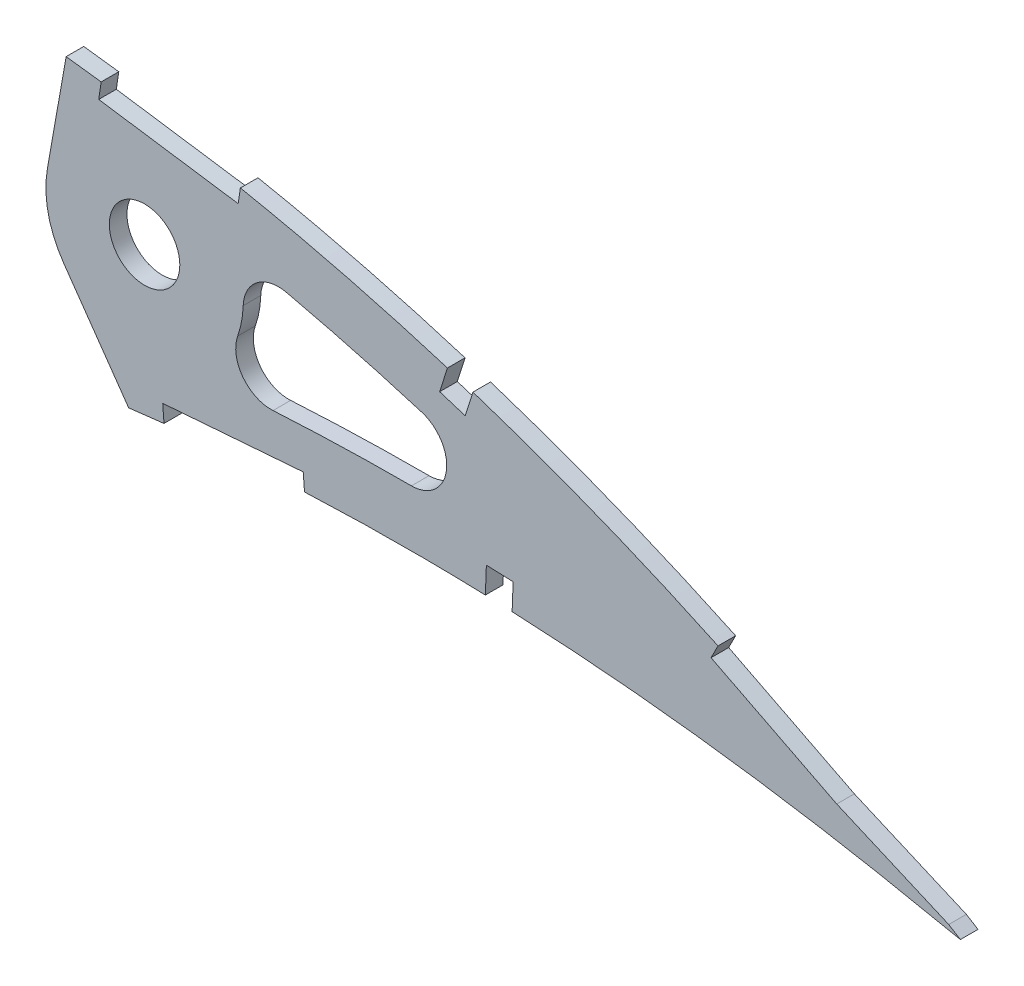
SolidWorks part; units mm, degrees
material "Pine"
ref_plane "Front Plane" through (0, 0, 0) normal (0, 0, 1) x (1, 0, 0)
ref_plane "Top Plane" through (0, 0, 0) normal (0, 1, 0) x (1, 0, 0)
ref_plane "Right Plane" through (0, 0, 0) normal (1, 0, 0) x (0, 0, -1)
curve "Curve2"
  spline degree 3 poles (520.229, 0.8111, 0) (520.1892, 0.8357, 0) (520.0299, 0.9341, 0) (519.6711, 1.1542, 0) (519.0735, 1.5208, 0) (518.237, 2.0313, 0) (517.1622, 2.6844, 0) (515.8486, 3.4756, 0) (514.2969, 4.4021, 0) (512.5075, 5.4598, 0) (510.4807, 6.6436, 0) (508.2172, 7.9486, 0) (505.7172, 9.3676, 0) (502.9816, 10.8948, 0) (500.0114, 12.5227, 0) (496.8072, 14.2443, 0) (493.3701, 16.0505, 0) (489.7015, 17.9338, 0) (485.8019, 19.8836, 0) (481.6733, 21.8919, 0) (477.317, 23.9487, 0) (472.7345, 26.0429, 0) (467.9284, 28.1661, 0) (462.9001, 30.305, 0) (457.6524, 32.4505, 0) (452.1876, 34.5902, 0) (446.5089, 36.7144, 0) (440.6184, 38.8094, 0) (434.5207, 40.866, 0) (428.2186, 42.8708, 0) (421.7166, 44.813, 0) (415.0186, 46.68, 0) (408.1302, 48.4622, 0) (401.0555, 50.1466, 0) (393.8008, 51.7219, 0) (386.3718, 53.1787, 0) (378.7746, 54.5024, 0) (371.0303, 55.692, 0) (363.2636, 56.6815, 0) (355.5128, 57.652, 0) (347.7736, 58.5637, 0) (339.9398, 59.4368, 0) (332.019, 60.2663, 0) (324.019, 61.0497, 0) (315.9478, 61.7836, 0) (307.814, 62.4658, 0) (299.6253, 63.0925, 0) (291.3904, 63.6628, 0) (283.1174, 64.1714, 0) (274.8152, 64.6183, 0) (266.4922, 65.0001, 0) (258.157, 65.3142, 0) (249.8185, 65.5589, 0) (241.4854, 65.7316, 0) (233.1666, 65.8314, 0) (224.8708, 65.8555, 0) (216.6071, 65.8035, 0) (208.384, 65.6736, 0) (200.2107, 65.464, 0) (192.0958, 65.1743, 0) (184.048, 64.8046, 0) (176.0762, 64.3519, 0) (168.189, 63.8191, 0) (160.3952, 63.2038, 0) (152.7034, 62.506, 0) (145.1216, 61.7286, 0) (137.6583, 60.8693, 0) (130.3214, 59.9308, 0) (123.1191, 58.9147, 0) (116.0593, 57.8206, 0) (109.1496, 56.6517, 0) (102.3976, 55.409, 0) (95.8102, 54.0963, 0) (89.3948, 52.714, 0) (83.1581, 51.266, 0) (77.1065, 49.7551, 0) (71.2467, 48.1838, 0) (65.5845, 46.5561, 0) (60.1256, 44.8756, 0) (54.8764, 43.1442, 0) (49.8409, 41.3683, 0) (45.0253, 39.5493, 0) (40.4333, 37.6928, 0) (36.0702, 35.8014, 0) (31.9393, 33.8806, 0) (28.0452, 31.9329, 0) (24.3908, 29.9636, 0) (20.9797, 27.9757, 0) (17.8153, 25.973, 0) (14.8987, 23.9604, 0) (12.2341, 21.9394, 0) (9.8224, 19.9149, 0) (7.6651, 17.8901, 0) (5.7652, 15.8664, 0) (4.1228, 13.8473, 0) (2.7399, 11.8344, 0) (1.6168, 9.8297, 0) (0.7561, 7.8345, 0) (0.1568, 5.85, 0) (-0.1712, 3.8792, 0) (-0.2528, 1.9205, 0) (-0.0842, 0.6392, 0) (0, 0, 0) knots 0 0 0 0 0.000254 0.001015 0.002283 0.004057 0.006331 0.009105 0.012374 0.016134 0.02038 0.025106 0.030306 0.035972 0.0421 0.048678 0.055702 0.06316 0.071046 0.07935 0.088063 0.097176 0.106678 0.116562 0.126814 0.137428 0.148394 0.1597 0.171338 0.183298 0.19557 0.208144 0.221012 0.234162 0.247587 0.261277 0.275223 0.289414 0.303771 0.317689 0.331784 0.34604 0.360444 0.374983 0.38964 0.404403 0.419257 0.434187 0.449177 0.464215 0.479284 0.49437 0.509458 0.524532 0.539579 0.554583 0.56953 0.584403 0.599191 0.613877 0.628447 0.642889 0.657186 0.671326 0.685294 0.699078 0.712665 0.726043 0.739198 0.752118 0.764792 0.777208 0.789356 0.801224 0.812804 0.824083 0.835055 0.84571 0.856038 0.866034 0.875689 0.884998 0.893953 0.902553 0.910789 0.918661 0.926166 0.933303 0.940071 0.946475 0.952518 0.958205 0.963547 0.968557 0.97325 0.977651 0.981787 0.985694 0.989415 0.993001 0.996508 1 1 1 1
curve "Curve3"
  spline degree 3 poles (0, 0, 0) (0.1336, -0.6306, 0) (0.4014, -1.8948, 0) (1.129, -3.7148, 0) (2.0912, -5.4642, 0) (3.3081, -7.1386, 0) (4.7718, -8.7374, 0) (6.479, -10.2623, 0) (8.428, -11.7125, 0) (10.6162, -13.0874, 0) (13.0406, -14.3883, 0) (15.6982, -15.6145, 0) (18.5868, -16.7656, 0) (21.7032, -17.8401, 0) (25.0435, -18.8396, 0) (28.6046, -19.7616, 0) (32.3825, -20.6074, 0) (36.3735, -21.375, 0) (40.5732, -22.065, 0) (44.9774, -22.6771, 0) (49.5814, -23.2117, 0) (54.3808, -23.6676, 0) (59.3708, -24.0458, 0) (64.5464, -24.3466, 0) (69.9027, -24.5709, 0) (75.4344, -24.718, 0) (81.1363, -24.7899, 0) (87.003, -24.788, 0) (93.0289, -24.7115, 0) (99.2088, -24.5648, 0) (105.5368, -24.3469, 0) (112.0073, -24.0604, 0) (118.6142, -23.7083, 0) (125.3518, -23.2917, 0) (132.2141, -22.8125, 0) (139.1951, -22.2745, 0) (146.2885, -21.679, 0) (153.4882, -21.0296, 0) (160.7876, -20.3295, 0) (168.1806, -19.5808, 0) (175.6606, -18.7872, 0) (183.2209, -17.9512, 0) (190.8551, -17.0772, 0) (198.5563, -16.1668, 0) (206.3179, -15.2253, 0) (214.1326, -14.2544, 0) (221.9939, -13.2579, 0) (229.8947, -12.2404, 0) (237.8276, -11.2019, 0) (245.786, -10.1497, 0) (253.7621, -9.0829, 0) (261.7491, -8.0072, 0) (269.7395, -6.9257, 0) (277.7256, -5.8389, 0) (285.7003, -4.7513, 0) (293.6562, -3.6657, 0) (301.5856, -2.5824, 0) (309.4812, -1.5067, 0) (317.3352, -0.4385, 0) (325.1402, 0.6201, 0) (332.8888, 1.6659, 0) (340.5737, 2.6975, 0) (348.187, 3.7144, 0) (355.721, 4.7168, 0) (363.0553, 5.6745, 0) (370.1707, 6.6383, 0) (377.0913, 7.4284, 0) (383.9258, 8.1028, 0) (390.6811, 8.6557, 0) (397.3493, 9.0951, 0) (403.9227, 9.4241, 0) (410.3934, 9.6473, 0) (416.7532, 9.7713, 0) (422.9943, 9.7993, 0) (429.1081, 9.7402, 0) (435.0867, 9.5987, 0) (440.9216, 9.3813, 0) (446.6049, 9.0952, 0) (452.1283, 8.7483, 0) (457.4837, 8.3456, 0) (462.6634, 7.8966, 0) (467.6597, 7.4078, 0) (472.4647, 6.8849, 0) (477.0715, 6.3387, 0) (481.4727, 5.7729, 0) (485.6616, 5.1968, 0) (489.6316, 4.6162, 0) (493.3764, 4.0385, 0) (496.89, 3.4693, 0) (500.1667, 2.916, 0) (503.2016, 2.384, 0) (505.9892, 1.8782, 0) (508.5257, 1.4052, 0) (510.8062, 0.9673, 0) (512.8275, 0.5717, 0) (514.5859, 0.2202, 0) (516.0789, -0.0824, 0) (517.3037, -0.3347, 0) (518.2586, -0.5328, 0) (518.9417, -0.6767, 0) (519.3522, -0.7624, 0) (519.5346, -0.8013, 0) (519.5802, -0.8111, 0) knots 0 0 0 0 0.003638 0.007293 0.011028 0.014901 0.018963 0.023258 0.027821 0.032679 0.037853 0.043362 0.049215 0.055422 0.061989 0.068918 0.076211 0.083868 0.091887 0.100266 0.109 0.118085 0.127515 0.137285 0.147388 0.157816 0.168563 0.179619 0.190977 0.202627 0.21456 0.226767 0.239236 0.251959 0.264924 0.27812 0.291536 0.30516 0.318981 0.332985 0.347163 0.361499 0.375981 0.390597 0.405333 0.420175 0.43511 0.450124 0.465203 0.480333 0.495501 0.51069 0.525887 0.541078 0.556247 0.571382 0.586466 0.601485 0.616424 0.631269 0.646007 0.660621 0.675098 0.689423 0.703582 0.716908 0.730009 0.742952 0.755726 0.76832 0.780724 0.792927 0.804916 0.816679 0.828204 0.839475 0.850481 0.861208 0.871639 0.881763 0.891564 0.901027 0.910139 0.918884 0.927249 0.935221 0.942785 0.949928 0.956638 0.962904 0.968712 0.974054 0.978918 0.983297 0.98718 0.990561 0.993433 0.995791 0.99763 0.998946 0.999737 1 1 1 1
sketch "Sketch1" plane through (0, 0, 0) normal (0, 0, 1) x (1, 0, 0)
  line L1 (502.7977, -0.7849) -> (507.4667, -1.7115)
  line L2 (503.4256, 0.7849) -> (507.4667, -1.7115)
  spline S2 degree 3 poles (0, 0) (0.1293, -0.6103) (0.3884, -1.8336) (1.0925, -3.5948) (2.0236, -5.2877) (3.2013, -6.908) (4.6177, -8.4552) (6.2698, -9.9309) (8.1558, -11.3342) (10.2733, -12.6647) (12.6193, -13.9236) (15.1912, -15.1102) (17.9865, -16.2241) (21.0022, -17.2639) (24.2346, -18.231) (27.6807, -19.1233) (31.3366, -19.9418) (35.1986, -20.6846) (39.2627, -21.3523) (43.5246, -21.9446) (47.9799, -22.4619) (52.6243, -22.9031) (57.4531, -23.2691) (62.4616, -23.5602) (67.6448, -23.7773) (72.9979, -23.9196) (78.5156, -23.9892) (84.1928, -23.9873) (90.0241, -23.9133) (96.0044, -23.7713) (102.128, -23.5605) (108.3894, -23.2833) (114.783, -22.9425) (121.303, -22.5394) (127.9436, -22.0756) (134.6991, -21.555) (141.5634, -20.9788) (148.5305, -20.3504) (155.5942, -19.6728) (162.7484, -18.9484) (169.9867, -18.1804) (177.3029, -17.3713) (184.6905, -16.5256) (192.1429, -15.6446) (199.6538, -14.7335) (207.2161, -13.794) (214.8235, -12.8296) (222.4691, -11.845) (230.1458, -10.84) (237.8471, -9.8218) (245.5656, -8.7896) (253.2946, -7.7486) (261.0269, -6.702) (268.755, -5.6503) (276.4722, -4.5978) (284.1711, -3.5473) (291.8444, -2.499) (299.485, -1.458) (307.0852, -0.4243) (314.6382, 0.6001) (322.1365, 1.6121) (329.5732, 2.6104) (336.9406, 3.5944) (344.2312, 4.5645) (351.3286, 5.4912) (358.2142, 6.4239) (364.9113, 7.1885) (371.525, 7.8411) (378.0621, 8.3761) (384.5149, 8.8013) (390.876, 9.1197) (397.1377, 9.3357) (403.2921, 9.4557) (409.3316, 9.4828) (415.2479, 9.4256) (421.0334, 9.2887) (426.6799, 9.0783) (432.1795, 8.8014) (437.5246, 8.4657) (442.7069, 8.076) (447.7194, 7.6415) (452.5543, 7.1686) (457.2041, 6.6625) (461.6621, 6.134) (465.9211, 5.5865) (469.9748, 5.029) (473.8165, 4.4671) (477.4403, 3.9081) (480.8404, 3.3572) (484.0114, 2.8219) (486.9482, 2.3069) (489.6458, 1.8176) (492.1004, 1.3598) (494.3072, 0.9361) (496.2632, 0.5532) (497.9648, 0.2131) (499.4095, -0.0797) (500.5948, -0.3239) (501.5189, -0.5155) (502.1799, -0.6549) (502.5771, -0.7378) (502.7536, -0.7754) (502.7977, -0.7849) knots 0 0 0 0 0.003638 0.007293 0.011028 0.014901 0.018963 0.023258 0.027821 0.032679 0.037853 0.043362 0.049215 0.055422 0.061989 0.068918 0.076211 0.083868 0.091887 0.100266 0.109 0.118085 0.127515 0.137285 0.147388 0.157816 0.168563 0.179619 0.190977 0.202627 0.21456 0.226767 0.239236 0.251959 0.264924 0.27812 0.291536 0.30516 0.318981 0.332985 0.347163 0.361499 0.375981 0.390597 0.405333 0.420175 0.43511 0.450124 0.465203 0.480333 0.495501 0.51069 0.525887 0.541078 0.556247 0.571382 0.586466 0.601485 0.616424 0.631269 0.646007 0.660621 0.675098 0.689423 0.703582 0.716908 0.730009 0.742952 0.755726 0.76832 0.780724 0.792927 0.804916 0.816679 0.828204 0.839475 0.850481 0.861208 0.871639 0.881763 0.891564 0.901027 0.910139 0.918884 0.927249 0.935221 0.942785 0.949928 0.956638 0.962904 0.968712 0.974054 0.978918 0.983297 0.98718 0.990561 0.993433 0.995791 0.99763 0.998946 0.999737 1 1 1 1
  spline S3 degree 3 poles (503.4256, 0.7849) (503.3871, 0.8087) (503.2329, 0.9039) (502.8857, 1.1169) (502.3075, 1.4716) (501.498, 1.9657) (500.4579, 2.5977) (499.1867, 3.3633) (497.6851, 4.26) (495.9535, 5.2834) (493.9922, 6.429) (491.8018, 7.6919) (489.3825, 9.0651) (486.7353, 10.5429) (483.8611, 12.1183) (480.7604, 13.7842) (477.4343, 15.5321) (473.8841, 17.3545) (470.1105, 19.2413) (466.1153, 21.1848) (461.8997, 23.1751) (457.4652, 25.2017) (452.8143, 27.2563) (447.9484, 29.3262) (442.8702, 31.4023) (437.5819, 33.4729) (432.0866, 35.5285) (426.3865, 37.5558) (420.4857, 39.546) (414.3871, 41.4861) (408.0952, 43.3656) (401.6135, 45.1723) (394.9475, 46.8969) (388.1015, 48.5268) (381.0811, 50.0513) (373.8919, 51.461) (366.5401, 52.742) (359.046, 53.8931) (351.5302, 54.8507) (344.0298, 55.7898) (336.5405, 56.6721) (328.9598, 57.517) (321.2948, 58.3197) (313.5531, 59.0778) (305.7427, 59.788) (297.8716, 60.4482) (289.9474, 61.0547) (281.9785, 61.6064) (273.9728, 62.0987) (265.9387, 62.5311) (257.8845, 62.9006) (249.8186, 63.2046) (241.7494, 63.4413) (233.6854, 63.6085) (225.6353, 63.7051) (217.6075, 63.7284) (209.6107, 63.678) (201.6532, 63.5523) (193.7439, 63.3495) (185.8911, 63.0691) (178.1033, 62.7114) (170.3889, 62.2734) (162.7565, 61.7577) (155.2145, 61.1624) (147.7711, 60.4871) (140.4342, 59.7347) (133.2119, 58.9033) (126.1121, 57.995) (119.1423, 57.0118) (112.3106, 55.953) (105.6241, 54.8218) (99.0901, 53.6193) (92.7156, 52.349) (86.5074, 51.0113) (80.4721, 49.6101) (74.616, 48.148) (68.9454, 46.6275) (63.4661, 45.0524) (58.1835, 43.4261) (53.1039, 41.7506) (48.2311, 40.0321) (43.571, 38.2719) (39.1273, 36.4754) (34.9051, 34.645) (30.9076, 32.7863) (27.1393, 30.9015) (23.603, 28.9958) (20.3021, 27.0721) (17.2398, 25.134) (14.4175, 23.1865) (11.839, 21.2308) (9.5051, 19.2717) (7.4175, 17.3123) (5.579, 15.3539) (3.9896, 13.4) (2.6514, 11.4522) (1.5646, 9.5122) (0.7317, 7.5814) (0.1518, 5.6611) (-0.1657, 3.7539) (-0.2447, 1.8584) (-0.0814, 0.6186) (0, 0) knots 0 0 0 0 0.000254 0.001015 0.002283 0.004057 0.006331 0.009105 0.012374 0.016134 0.02038 0.025106 0.030306 0.035972 0.0421 0.048678 0.055702 0.06316 0.071046 0.07935 0.088063 0.097176 0.106678 0.116562 0.126814 0.137428 0.148394 0.1597 0.171338 0.183298 0.19557 0.208144 0.221012 0.234162 0.247587 0.261277 0.275223 0.289414 0.303771 0.317689 0.331784 0.34604 0.360444 0.374983 0.38964 0.404403 0.419257 0.434187 0.449177 0.464215 0.479284 0.49437 0.509458 0.524532 0.539579 0.554583 0.56953 0.584403 0.599191 0.613877 0.628447 0.642889 0.657186 0.671326 0.685294 0.699078 0.712665 0.726043 0.739198 0.752118 0.764792 0.777208 0.789356 0.801224 0.812804 0.824083 0.835055 0.84571 0.856038 0.866034 0.875689 0.884998 0.893953 0.902553 0.910789 0.918661 0.926166 0.933303 0.940071 0.946475 0.952518 0.958205 0.963547 0.968557 0.97325 0.977651 0.981787 0.985694 0.989415 0.993001 0.996508 1 1 1 1
extrude "Boss-Extrude1" add sketch "Sketch1" along normal blind 3.175
sketch "Sketch4" plane through (0, 0, 3.175) normal (0, 0, 1) x (1, 0, 0)
  line L0 (342.9777, 36.32) -> (346.3588, 55.4952)
  line L1 (345.923, 23.0344) -> (357.6226, 6.3256)
  line L2 (360.4876, 33.2326) -> (390.7312, 33.2326)
  circle A0 centre (360.4876, 33.2326) radius 17.78
  circle A1 centre (360.4876, 33.2326) radius 6.35
  spline S0 degree 3 poles (-1939.359, -486.1193) (49.033, 56.5957) (-7.3857, 17.6121) (1.0925, -3.5948) (2.0236, -5.2877) (3.2013, -6.908) (4.6177, -8.4552) (6.2698, -9.9309) (8.1558, -11.3342) (10.2733, -12.6647) (12.6193, -13.9236) (15.1912, -15.1102) (17.9865, -16.2241) (21.0022, -17.2639) (24.2346, -18.231) (27.6807, -19.1233) (31.3366, -19.9418) (35.1986, -20.6846) (39.2627, -21.3523) (43.5246, -21.9446) (47.9799, -22.4619) (52.6243, -22.9031) (57.4531, -23.2691) (62.4616, -23.5602) (67.6448, -23.7773) (72.9979, -23.9196) (78.5156, -23.9892) (84.1928, -23.9873) (90.0241, -23.9133) (96.0044, -23.7713) (102.128, -23.5605) (108.3894, -23.2833) (114.783, -22.9425) (121.303, -22.5394) (127.9436, -22.0756) (134.6991, -21.555) (141.5634, -20.9788) (148.5305, -20.3504) (155.5942, -19.6728) (162.7484, -18.9484) (169.9867, -18.1804) (177.3029, -17.3713) (184.6905, -16.5256) (192.1429, -15.6446) (199.6538, -14.7335) (207.2161, -13.794) (214.8235, -12.8296) (222.4691, -11.845) (230.1458, -10.84) (237.8471, -9.8218) (245.5656, -8.7896) (253.2946, -7.7486) (261.0269, -6.702) (268.755, -5.6503) (276.4722, -4.5978) (284.1711, -3.5473) (291.8444, -2.499) (299.485, -1.458) (307.0852, -0.4243) (314.6382, 0.6001) (322.1365, 1.6121) (329.5732, 2.6104) (336.9406, 3.5944) (344.2312, 4.5645) (351.3286, 5.4912) (358.2142, 6.4239) (364.9113, 7.1885) (371.525, 7.8411) (378.0621, 8.3761) (384.5149, 8.8013) (390.876, 9.1197) (397.1377, 9.3357) (403.2921, 9.4557) (409.3316, 9.4828) (415.2479, 9.4256) (421.0334, 9.2887) (426.6799, 9.0783) (432.1795, 8.8014) (437.5246, 8.4657) (442.7069, 8.076) (447.7194, 7.6415) (452.5543, 7.1686) (457.2041, 6.6625) (461.6621, 6.134) (465.9211, 5.5865) (469.9748, 5.029) (473.8165, 4.4671) (477.4403, 3.9081) (480.8404, 3.3572) (484.0114, 2.8219) (486.9482, 2.3069) (489.6458, 1.8176) (492.1004, 1.3598) (494.3072, 0.9361) (496.2632, 0.5532) (497.9648, 0.2131) (499.4095, -0.0797) (500.5948, -0.3239) (501.5189, -0.5155) (502.1799, -0.6549) (517.7197, -3.8983) (531.8047, -12.9312) (961.8177, 1945.365) knots -0.121768 -0.121768 -0.121768 -0.121768 0.003638 0.007293 0.011028 0.014901 0.018963 0.023258 0.027821 0.032679 0.037853 0.043362 0.049215 0.055422 0.061989 0.068918 0.076211 0.083868 0.091887 0.100266 0.109 0.118085 0.127515 0.137285 0.147388 0.157816 0.168563 0.179619 0.190977 0.202627 0.21456 0.226767 0.239236 0.251959 0.264924 0.27812 0.291536 0.30516 0.318981 0.332985 0.347163 0.361499 0.375981 0.390597 0.405333 0.420175 0.43511 0.450124 0.465203 0.480333 0.495501 0.51069 0.525887 0.541078 0.556247 0.571382 0.586466 0.601485 0.616424 0.631269 0.646007 0.660621 0.675098 0.689423 0.703582 0.716908 0.730009 0.742952 0.755726 0.76832 0.780724 0.792927 0.804916 0.816679 0.828204 0.839475 0.850481 0.861208 0.871639 0.881763 0.891564 0.901027 0.910139 0.918884 0.927249 0.935221 0.942785 0.949928 0.956638 0.962904 0.968712 0.974054 0.978918 0.983297 0.98718 0.990561 0.993433 0.995791 0.99763 0.998946 0.999737 1.090356 1.090356 1.090356 1.090356 only from (0, 0) to (502.7977, -0.7849) construction
  spline S1 degree 3 poles (1596.0847, 1675.4542) (530.0817, -21.8378) (517.9824, -8.1433) (502.8857, 1.1169) (502.3075, 1.4716) (501.498, 1.9657) (500.4579, 2.5977) (499.1867, 3.3633) (497.6851, 4.26) (495.9535, 5.2834) (493.9922, 6.429) (491.8018, 7.6919) (489.3825, 9.0651) (486.7353, 10.5429) (483.8611, 12.1183) (480.7604, 13.7842) (477.4343, 15.5321) (473.8841, 17.3545) (470.1105, 19.2413) (466.1153, 21.1848) (461.8997, 23.1751) (457.4652, 25.2017) (452.8143, 27.2563) (447.9484, 29.3262) (442.8702, 31.4023) (437.5819, 33.4729) (432.0866, 35.5285) (426.3865, 37.5558) (420.4857, 39.546) (414.3871, 41.4861) (408.0952, 43.3656) (401.6135, 45.1723) (394.9475, 46.8969) (388.1015, 48.5268) (381.0811, 50.0513) (373.8919, 51.461) (366.5401, 52.742) (359.046, 53.8931) (351.5302, 54.8507) (344.0298, 55.7898) (336.5405, 56.6721) (328.9598, 57.517) (321.2948, 58.3197) (313.5531, 59.0778) (305.7427, 59.788) (297.8716, 60.4482) (289.9474, 61.0547) (281.9785, 61.6064) (273.9728, 62.0987) (265.9387, 62.5311) (257.8845, 62.9006) (249.8186, 63.2046) (241.7494, 63.4413) (233.6854, 63.6085) (225.6353, 63.7051) (217.6075, 63.7284) (209.6107, 63.678) (201.6532, 63.5523) (193.7439, 63.3495) (185.8911, 63.0691) (178.1033, 62.7114) (170.3889, 62.2734) (162.7565, 61.7577) (155.2145, 61.1624) (147.7711, 60.4871) (140.4342, 59.7347) (133.2119, 58.9033) (126.1121, 57.995) (119.1423, 57.0118) (112.3106, 55.953) (105.6241, 54.8218) (99.0901, 53.6193) (92.7156, 52.349) (86.5074, 51.0113) (80.4721, 49.6101) (74.616, 48.148) (68.9454, 46.6275) (63.4661, 45.0524) (58.1835, 43.4261) (53.1039, 41.7506) (48.2311, 40.0321) (43.571, 38.2719) (39.1273, 36.4754) (34.9051, 34.645) (30.9076, 32.7863) (27.1393, 30.9015) (23.603, 28.9958) (20.3021, 27.0721) (17.2398, 25.134) (14.4175, 23.1865) (11.839, 21.2308) (9.5051, 19.2717) (7.4175, 17.3123) (5.579, 15.3539) (3.9896, 13.4) (2.6514, 11.4522) (1.5646, 9.5122) (0.7317, 7.5814) (0.1518, 5.6611) (-0.1657, 3.7539) (-1.1153, -19.0274) (65.1985, -36.9717) (-1990.693, -186.6939) knots -0.096988 -0.096988 -0.096988 -0.096988 0.000254 0.001015 0.002283 0.004057 0.006331 0.009105 0.012374 0.016134 0.02038 0.025106 0.030306 0.035972 0.0421 0.048678 0.055702 0.06316 0.071046 0.07935 0.088063 0.097176 0.106678 0.116562 0.126814 0.137428 0.148394 0.1597 0.171338 0.183298 0.19557 0.208144 0.221012 0.234162 0.247587 0.261277 0.275223 0.289414 0.303771 0.317689 0.331784 0.34604 0.360444 0.374983 0.38964 0.404403 0.419257 0.434187 0.449177 0.464215 0.479284 0.49437 0.509458 0.524532 0.539579 0.554583 0.56953 0.584403 0.599191 0.613877 0.628447 0.642889 0.657186 0.671326 0.685294 0.699078 0.712665 0.726043 0.739198 0.752118 0.764792 0.777208 0.789356 0.801224 0.812804 0.824083 0.835055 0.84571 0.856038 0.866034 0.875689 0.884998 0.893953 0.902553 0.910789 0.918661 0.926166 0.933303 0.940071 0.946475 0.952518 0.958205 0.963547 0.968557 0.97325 0.977651 0.981787 0.985694 0.989415 0.993001 0.996508 1.116632 1.116632 1.116632 1.116632 only from (503.4256, 0.7849) to (0, 0) construction
  spline S2 degree 3 poles (0, 0) (0.1293, -0.6103) (0.3884, -1.8336) (1.0925, -3.5948) (2.0236, -5.2877) (3.2013, -6.908) (4.6177, -8.4552) (6.2698, -9.9309) (8.1558, -11.3342) (10.2733, -12.6647) (12.6193, -13.9236) (15.1912, -15.1102) (17.9865, -16.2241) (21.0022, -17.2639) (24.2346, -18.231) (27.6807, -19.1233) (31.3366, -19.9418) (35.1986, -20.6846) (39.2627, -21.3523) (43.5246, -21.9446) (47.9799, -22.4619) (52.6243, -22.9031) (57.4531, -23.2691) (62.4616, -23.5602) (67.6448, -23.7773) (72.9979, -23.9196) (78.5156, -23.9892) (84.1928, -23.9873) (90.0241, -23.9133) (96.0044, -23.7713) (102.128, -23.5605) (108.3894, -23.2833) (114.783, -22.9425) (121.303, -22.5394) (127.9436, -22.0756) (134.6991, -21.555) (141.5634, -20.9788) (148.5305, -20.3504) (155.5942, -19.6728) (162.7484, -18.9484) (169.9867, -18.1804) (177.3029, -17.3713) (184.6905, -16.5256) (192.1429, -15.6446) (199.6538, -14.7335) (207.2161, -13.794) (214.8235, -12.8296) (222.4691, -11.845) (230.1458, -10.84) (237.8471, -9.8218) (245.5656, -8.7896) (253.2946, -7.7486) (261.0269, -6.702) (268.755, -5.6503) (276.4722, -4.5978) (284.1711, -3.5473) (291.8444, -2.499) (299.485, -1.458) (307.0852, -0.4243) (314.6382, 0.6001) (322.1365, 1.6121) (329.5732, 2.6104) (336.9406, 3.5944) (344.2312, 4.5645) (351.3286, 5.4912) (358.2142, 6.4239) (364.9113, 7.1885) (371.525, 7.8411) (378.0621, 8.3761) (384.5149, 8.8013) (390.876, 9.1197) (397.1377, 9.3357) (403.2921, 9.4557) (409.3316, 9.4828) (415.2479, 9.4256) (421.0334, 9.2887) (426.6799, 9.0783) (432.1795, 8.8014) (437.5246, 8.4657) (442.7069, 8.076) (447.7194, 7.6415) (452.5543, 7.1686) (457.2041, 6.6625) (461.6621, 6.134) (465.9211, 5.5865) (469.9748, 5.029) (473.8165, 4.4671) (477.4403, 3.9081) (480.8404, 3.3572) (484.0114, 2.8219) (486.9482, 2.3069) (489.6458, 1.8176) (492.1004, 1.3598) (494.3072, 0.9361) (496.2632, 0.5532) (497.9648, 0.2131) (499.4095, -0.0797) (500.5948, -0.3239) (501.5189, -0.5155) (502.1799, -0.6549) (502.5771, -0.7378) (502.7536, -0.7754) (502.7977, -0.7849) knots 0 0 0 0 0.003638 0.007293 0.011028 0.014901 0.018963 0.023258 0.027821 0.032679 0.037853 0.043362 0.049215 0.055422 0.061989 0.068918 0.076211 0.083868 0.091887 0.100266 0.109 0.118085 0.127515 0.137285 0.147388 0.157816 0.168563 0.179619 0.190977 0.202627 0.21456 0.226767 0.239236 0.251959 0.264924 0.27812 0.291536 0.30516 0.318981 0.332985 0.347163 0.361499 0.375981 0.390597 0.405333 0.420175 0.43511 0.450124 0.465203 0.480333 0.495501 0.51069 0.525887 0.541078 0.556247 0.571382 0.586466 0.601485 0.616424 0.631269 0.646007 0.660621 0.675098 0.689423 0.703582 0.716908 0.730009 0.742952 0.755726 0.76832 0.780724 0.792927 0.804916 0.816679 0.828204 0.839475 0.850481 0.861208 0.871639 0.881763 0.891564 0.901027 0.910139 0.918884 0.927249 0.935221 0.942785 0.949928 0.956638 0.962904 0.968712 0.974054 0.978918 0.983297 0.98718 0.990561 0.993433 0.995791 0.99763 0.998946 0.999737 1 1 1 1
  spline S3 degree 3 poles (503.4256, 0.7849) (503.3871, 0.8087) (503.2329, 0.9039) (502.8857, 1.1169) (502.3075, 1.4716) (501.498, 1.9657) (500.4579, 2.5977) (499.1867, 3.3633) (497.6851, 4.26) (495.9535, 5.2834) (493.9922, 6.429) (491.8018, 7.6919) (489.3825, 9.0651) (486.7353, 10.5429) (483.8611, 12.1183) (480.7604, 13.7842) (477.4343, 15.5321) (473.8841, 17.3545) (470.1105, 19.2413) (466.1153, 21.1848) (461.8997, 23.1751) (457.4652, 25.2017) (452.8143, 27.2563) (447.9484, 29.3262) (442.8702, 31.4023) (437.5819, 33.4729) (432.0866, 35.5285) (426.3865, 37.5558) (420.4857, 39.546) (414.3871, 41.4861) (408.0952, 43.3656) (401.6135, 45.1723) (394.9475, 46.8969) (388.1015, 48.5268) (381.0811, 50.0513) (373.8919, 51.461) (366.5401, 52.742) (359.046, 53.8931) (351.5302, 54.8507) (344.0298, 55.7898) (336.5405, 56.6721) (328.9598, 57.517) (321.2948, 58.3197) (313.5531, 59.0778) (305.7427, 59.788) (297.8716, 60.4482) (289.9474, 61.0547) (281.9785, 61.6064) (273.9728, 62.0987) (265.9387, 62.5311) (257.8845, 62.9006) (249.8186, 63.2046) (241.7494, 63.4413) (233.6854, 63.6085) (225.6353, 63.7051) (217.6075, 63.7284) (209.6107, 63.678) (201.6532, 63.5523) (193.7439, 63.3495) (185.8911, 63.0691) (178.1033, 62.7114) (170.3889, 62.2734) (162.7565, 61.7577) (155.2145, 61.1624) (147.7711, 60.4871) (140.4342, 59.7347) (133.2119, 58.9033) (126.1121, 57.995) (119.1423, 57.0118) (112.3106, 55.953) (105.6241, 54.8218) (99.0901, 53.6193) (92.7156, 52.349) (86.5074, 51.0113) (80.4721, 49.6101) (74.616, 48.148) (68.9454, 46.6275) (63.4661, 45.0524) (58.1835, 43.4261) (53.1039, 41.7506) (48.2311, 40.0321) (43.571, 38.2719) (39.1273, 36.4754) (34.9051, 34.645) (30.9076, 32.7863) (27.1393, 30.9015) (23.603, 28.9958) (20.3021, 27.0721) (17.2398, 25.134) (14.4175, 23.1865) (11.839, 21.2308) (9.5051, 19.2717) (7.4175, 17.3123) (5.579, 15.3539) (3.9896, 13.4) (2.6514, 11.4522) (1.5646, 9.5122) (0.7317, 7.5814) (0.1518, 5.6611) (-0.1657, 3.7539) (-0.2447, 1.8584) (-0.0814, 0.6186) (0, 0) knots 0 0 0 0 0.000254 0.001015 0.002283 0.004057 0.006331 0.009105 0.012374 0.016134 0.02038 0.025106 0.030306 0.035972 0.0421 0.048678 0.055702 0.06316 0.071046 0.07935 0.088063 0.097176 0.106678 0.116562 0.126814 0.137428 0.148394 0.1597 0.171338 0.183298 0.19557 0.208144 0.221012 0.234162 0.247587 0.261277 0.275223 0.289414 0.303771 0.317689 0.331784 0.34604 0.360444 0.374983 0.38964 0.404403 0.419257 0.434187 0.449177 0.464215 0.479284 0.49437 0.509458 0.524532 0.539579 0.554583 0.56953 0.584403 0.599191 0.613877 0.628447 0.642889 0.657186 0.671326 0.685294 0.699078 0.712665 0.726043 0.739198 0.752118 0.764792 0.777208 0.789356 0.801224 0.812804 0.824083 0.835055 0.84571 0.856038 0.866034 0.875689 0.884998 0.893953 0.902553 0.910789 0.918661 0.926166 0.933303 0.940071 0.946475 0.952518 0.958205 0.963547 0.968557 0.97325 0.977651 0.981787 0.985694 0.989415 0.993001 0.996508 1 1 1 1
  spline S4 degree 1 poles (498.0859, -7.8588) (10.022, 1.7185) knots 0 0 1 1 construction
  spline S5 degree 1 poles (10.022, 1.7185) (504.9173, 9.1516) knots 0 0 1 1 construction
  spline S6 degree 3 poles (498.0859, -7.8588) (497.9469, -7.7729) (497.6755, -7.6063) (497.0745, -7.2376) (496.073, -6.6257) (494.034, -5.3896) (489.9509, -2.9592) (481.7087, 1.7828) (464.948, 10.7477) (440.2507, 22.0083) (414.6791, 31.031) (393.8046, 36.8155) (380.602, 39.8235) (369.9822, 41.8499) (361.9478, 43.1977) (353.9876, 44.3116) (345.6865, 45.3455) (337.4905, 46.3384) (326.5045, 47.5759) (307.2867, 49.5386) (279.7715, 51.732) (246.7179, 53.3195) (213.6646, 53.7552) (180.6691, 52.9014) (147.8152, 50.5632) (120.6625, 47.1646) (99.1877, 43.3787) (83.2589, 39.9382) (67.5746, 35.8064) (54.8041, 31.6869) (44.8785, 27.8959) (37.6273, 24.7728) (30.6423, 21.3346) (24.0439, 17.5382) (18.0447, 13.3493) (13.8923, 9.5446) (11.5209, 6.5233) (10.5748, 4.8197) (10.1543, 3.6588) (10.0297, 3.1195) (9.9672, 2.6225) (9.9572, 2.3998) (9.9588, 2.3191) (9.9601, 2.2824) (9.9755, 2.1081) (9.998, 1.9117) (10.0142, 1.7801) (10.022, 1.7185) knots 0 0 0 0 0.000976 0.001952 0.003903 0.007806 0.015612 0.031224 0.062448 0.124896 0.187344 0.218568 0.249792 0.265404 0.281016 0.296629 0.312241 0.327853 0.343465 0.374689 0.437137 0.499585 0.562033 0.624481 0.686929 0.749377 0.780601 0.811825 0.843049 0.874274 0.889886 0.905498 0.92111 0.936722 0.952334 0.967946 0.975752 0.983558 0.987461 0.991364 0.993315 0.995267 0.996242 0.997218 0.998194 0.998682 0.99917 0.99917 0.99917 0.99917
  spline S7 degree 3 poles (10.022, 1.7185) (10.0347, 1.6599) (10.0621, 1.5353) (10.1053, 1.3469) (10.1485, 1.1764) (10.1634, 1.1269) (10.1846, 1.0623) (10.2582, 0.8739) (10.471, 0.4378) (10.7582, -0.0307) (11.4745, -0.9405) (12.8348, -2.2117) (15.8465, -4.2506) (20.7309, -6.5276) (27.4244, -8.6509) (34.5678, -10.2856) (41.9694, -11.5214) (49.5311, -12.4386) (59.7521, -13.3077) (72.7026, -13.8464) (88.3798, -13.8504) (104.1321, -13.363) (125.1917, -12.1985) (151.5744, -9.9789) (183.2656, -6.5394) (214.9809, -2.61) (246.7126, 1.5971) (278.4754, 5.9283) (304.9613, 9.5471) (323.5218, 12.0515) (334.1258, 13.4688) (340.757, 14.3528) (346.0757, 15.0514) (350.0239, 15.5708) (353.9954, 16.1055) (358.0945, 16.6309) (362.1894, 17.1023) (367.6256, 17.6763) (377.1849, 18.5459) (390.8533, 19.3786) (412.7664, 19.8538) (440.1321, 18.8575) (467.3149, 15.8619) (486.1639, 12.8099) (495.5577, 11.0534) (499.8832, 10.1925) (501.9026, 9.7801) (502.8845, 9.5777) (503.7571, 9.3959) (504.3754, 9.2659) (504.7415, 9.1891) (504.9173, 9.1516) knots 0.000865 0.000865 0.000865 0.000865 0.001353 0.00184 0.002816 0.003792 0.004768 0.006719 0.008671 0.012573 0.016476 0.024282 0.032088 0.047699 0.063311 0.078922 0.094534 0.110145 0.125757 0.15698 0.188203 0.219426 0.250649 0.313095 0.37554 0.437986 0.500432 0.562878 0.625324 0.656547 0.672159 0.68777 0.695576 0.703382 0.711187 0.718993 0.726799 0.734605 0.750216 0.781439 0.812662 0.875108 0.937554 0.968777 0.984389 0.992194 0.994146 0.996097 0.998049 0.999024 1 1 1 1
  spline M12 degree 3 poles (503.4256, 0.7849) (503.3871, 0.8087) (503.2329, 0.9039) (502.8857, 1.1169) (502.3075, 1.4716) (501.498, 1.9657) (500.4579, 2.5977) (499.1867, 3.3633) (497.6851, 4.26) (495.9535, 5.2834) (493.9922, 6.429) (491.8018, 7.6919) (489.3825, 9.0651) (486.7353, 10.5429) (483.8611, 12.1183) (480.7604, 13.7842) (477.4343, 15.5321) (473.8841, 17.3545) (470.1105, 19.2413) (466.1153, 21.1848) (461.8997, 23.1751) (457.4652, 25.2017) (452.8143, 27.2563) (447.9484, 29.3262) (442.8702, 31.4023) (437.5819, 33.4729) (432.0866, 35.5285) (426.3865, 37.5558) (420.4857, 39.546) (414.3871, 41.4861) (408.0952, 43.3656) (401.6135, 45.1723) (394.9475, 46.8969) (388.1015, 48.5268) (381.0811, 50.0513) (373.8919, 51.461) (366.5401, 52.742) (359.046, 53.8931) (351.5302, 54.8507) (344.0298, 55.7898) (336.5405, 56.6721) (328.9598, 57.517) (321.2948, 58.3197) (313.5531, 59.0778) (305.7427, 59.788) (297.8716, 60.4482) (289.9474, 61.0547) (281.9785, 61.6064) (273.9728, 62.0987) (265.9387, 62.5311) (257.8845, 62.9006) (249.8186, 63.2046) (241.7494, 63.4413) (233.6854, 63.6085) (225.6353, 63.7051) (217.6075, 63.7284) (209.6107, 63.678) (201.6532, 63.5523) (193.7439, 63.3495) (185.8911, 63.0691) (178.1033, 62.7114) (170.3889, 62.2734) (162.7565, 61.7577) (155.2145, 61.1624) (147.7711, 60.4871) (140.4342, 59.7347) (133.2119, 58.9033) (126.1121, 57.995) (119.1423, 57.0118) (112.3106, 55.953) (105.6241, 54.8218) (99.0901, 53.6193) (92.7156, 52.349) (86.5074, 51.0113) (80.4721, 49.6101) (74.616, 48.148) (68.9454, 46.6275) (63.4661, 45.0524) (58.1835, 43.4261) (53.1039, 41.7506) (48.2311, 40.0321) (43.571, 38.2719) (39.1273, 36.4754) (34.9051, 34.645) (30.9076, 32.7863) (27.1393, 30.9015) (23.603, 28.9958) (20.3021, 27.0721) (17.2398, 25.134) (14.4175, 23.1865) (11.839, 21.2308) (9.5051, 19.2717) (7.4175, 17.3123) (5.579, 15.3539) (3.9896, 13.4) (2.6514, 11.4522) (1.5646, 9.5122) (0.7317, 7.5814) (0.1518, 5.6611) (-0.1657, 3.7539) (-0.2447, 1.8584) (-0.0814, 0.6186) (0, 0) knots 0 0 0 0 0.000254 0.001015 0.002283 0.004057 0.006331 0.009105 0.012374 0.016134 0.02038 0.025106 0.030306 0.035972 0.0421 0.048678 0.055702 0.06316 0.071046 0.07935 0.088063 0.097176 0.106678 0.116562 0.126814 0.137428 0.148394 0.1597 0.171338 0.183298 0.19557 0.208144 0.221012 0.234162 0.247587 0.261277 0.275223 0.289414 0.303771 0.317689 0.331784 0.34604 0.360444 0.374983 0.38964 0.404403 0.419257 0.434187 0.449177 0.464215 0.479284 0.49437 0.509458 0.524532 0.539579 0.554583 0.56953 0.584403 0.599191 0.613877 0.628447 0.642889 0.657186 0.671326 0.685294 0.699078 0.712665 0.726043 0.739198 0.752118 0.764792 0.777208 0.789356 0.801224 0.812804 0.824083 0.835055 0.84571 0.856038 0.866034 0.875689 0.884998 0.893953 0.902553 0.910789 0.918661 0.926166 0.933303 0.940071 0.946475 0.952518 0.958205 0.963547 0.968557 0.97325 0.977651 0.981787 0.985694 0.989415 0.993001 0.996508 1 1 1 1
  spline M13 degree 3 poles (0, 0) (0.1293, -0.6103) (0.3884, -1.8336) (1.0925, -3.5948) (2.0236, -5.2877) (3.2013, -6.908) (4.6177, -8.4552) (6.2698, -9.9309) (8.1558, -11.3342) (10.2733, -12.6647) (12.6193, -13.9236) (15.1912, -15.1102) (17.9865, -16.2241) (21.0022, -17.2639) (24.2346, -18.231) (27.6807, -19.1233) (31.3366, -19.9418) (35.1986, -20.6846) (39.2627, -21.3523) (43.5246, -21.9446) (47.9799, -22.4619) (52.6243, -22.9031) (57.4531, -23.2691) (62.4616, -23.5602) (67.6448, -23.7773) (72.9979, -23.9196) (78.5156, -23.9892) (84.1928, -23.9873) (90.0241, -23.9133) (96.0044, -23.7713) (102.128, -23.5605) (108.3894, -23.2833) (114.783, -22.9425) (121.303, -22.5394) (127.9436, -22.0756) (134.6991, -21.555) (141.5634, -20.9788) (148.5305, -20.3504) (155.5942, -19.6728) (162.7484, -18.9484) (169.9867, -18.1804) (177.3029, -17.3713) (184.6905, -16.5256) (192.1429, -15.6446) (199.6538, -14.7335) (207.2161, -13.794) (214.8235, -12.8296) (222.4691, -11.845) (230.1458, -10.84) (237.8471, -9.8218) (245.5656, -8.7896) (253.2946, -7.7486) (261.0269, -6.702) (268.755, -5.6503) (276.4722, -4.5978) (284.1711, -3.5473) (291.8444, -2.499) (299.485, -1.458) (307.0852, -0.4243) (314.6382, 0.6001) (322.1365, 1.6121) (329.5732, 2.6104) (336.9406, 3.5944) (344.2312, 4.5645) (351.3286, 5.4912) (358.2142, 6.4239) (364.9113, 7.1885) (371.525, 7.8411) (378.0621, 8.3761) (384.5149, 8.8013) (390.876, 9.1197) (397.1377, 9.3357) (403.2921, 9.4557) (409.3316, 9.4828) (415.2479, 9.4256) (421.0334, 9.2887) (426.6799, 9.0783) (432.1795, 8.8014) (437.5246, 8.4657) (442.7069, 8.076) (447.7194, 7.6415) (452.5543, 7.1686) (457.2041, 6.6625) (461.6621, 6.134) (465.9211, 5.5865) (469.9748, 5.029) (473.8165, 4.4671) (477.4403, 3.9081) (480.8404, 3.3572) (484.0114, 2.8219) (486.9482, 2.3069) (489.6458, 1.8176) (492.1004, 1.3598) (494.3072, 0.9361) (496.2632, 0.5532) (497.9648, 0.2131) (499.4095, -0.0797) (500.5948, -0.3239) (501.5189, -0.5155) (502.1799, -0.6549) (502.5771, -0.7378) (502.7536, -0.7754) (502.7977, -0.7849) knots 0 0 0 0 0.003638 0.007293 0.011028 0.014901 0.018963 0.023258 0.027821 0.032679 0.037853 0.043362 0.049215 0.055422 0.061989 0.068918 0.076211 0.083868 0.091887 0.100266 0.109 0.118085 0.127515 0.137285 0.147388 0.157816 0.168563 0.179619 0.190977 0.202627 0.21456 0.226767 0.239236 0.251959 0.264924 0.27812 0.291536 0.30516 0.318981 0.332985 0.347163 0.361499 0.375981 0.390597 0.405333 0.420175 0.43511 0.450124 0.465203 0.480333 0.495501 0.51069 0.525887 0.541078 0.556247 0.571382 0.586466 0.601485 0.616424 0.631269 0.646007 0.660621 0.675098 0.689423 0.703582 0.716908 0.730009 0.742952 0.755726 0.76832 0.780724 0.792927 0.804916 0.816679 0.828204 0.839475 0.850481 0.861208 0.871639 0.881763 0.891564 0.901027 0.910139 0.918884 0.927249 0.935221 0.942785 0.949928 0.956638 0.962904 0.968712 0.974054 0.978918 0.983297 0.98718 0.990561 0.993433 0.995791 0.99763 0.998946 0.999737 1 1 1 1
  dimension "D1" = 35.56
  dimension "D3" = 80
  dimension "D4" = 55
  dimension "D2" = 10.16
extrude "Cut-Extrude2" cut sketch "Sketch4" against normal blind 7.62 contours S7 S6 L0 L1 M12 M13 | S6 S7 L1 A0 L0 | A0 S7 S6 | A1 region at (177.667, 21.0378, 3.175) region at (354.3172, 33.2326, 3.175) region at (170.7027, 55.7911, 3.175) region at (401.1233, 26.4422, 3.175)
sketch "Sketch5" plane through (0, 0, 3.175) normal (0, 0, 1) x (1, 0, 0)
  line L1 (352.6921, 54.8905) -> (352.2294, 51.7498)
  line L3 (377.8179, 51.1893) -> (352.6921, 54.8905)
  line L5 (415.1161, 41.459) -> (413.6569, 36.8603)
  line L7 (422.066, 14.0099) -> (421.8846, 9.1885)
  line L9 (426.8874, 13.8284) -> (422.066, 14.0099)
  line L11 (419.7148, 39.9998) -> (415.1161, 41.459)
  line L13 (463.9822, 22.6301) -> (462.5448, 19.7991)
  line L15 (486.5411, 11.1759) -> (463.9822, 22.6301)
  line L17 (509.7692, 1.1434) -> (486.5411, 11.1759)
  line L19 (389.0717, 12.0535) -> (363.7545, 10.0956)
  line L21 (363.7545, 10.0956) -> (363.9992, 6.9309)
  line L23 (363.9992, 6.9309) -> (389.3165, 8.8889)
  line L25 (389.3165, 8.8889) -> (389.0717, 12.0535)
  line L27 (352.2294, 51.7498) -> (377.3553, 48.0485)
  line L29 (377.3553, 48.0485) -> (377.8179, 51.1893)
  line L31 (421.8846, 9.1885) -> (426.706, 9.007)
  line L33 (426.706, 9.007) -> (426.8874, 13.8284)
  line L35 (413.6569, 36.8603) -> (418.2556, 35.4011)
  line L37 (418.2556, 35.4011) -> (419.7148, 39.9998)
  line L39 (462.5448, 19.7991) -> (485.1923, 8.3)
  line L41 (485.1923, 8.3) -> (508.5102, -1.7713)
  line L43 (508.5102, -1.7713) -> (509.7692, 1.1434)
extrude "Cut-Extrude3" cut sketch "Sketch5" against normal blind 7.62
fillet "Fillet1" radius 6.35 3 edges at (449.31, 17.6882, 1.5875) (369.3635, 17.8265, 1.5875) (376.692, 40.55, 1.5875)
move or copy body "Body-Move/Copy1" [suppressed] bodies to move or copy 118 parameters "D1"=0, "D2"=0, "D3"=0
